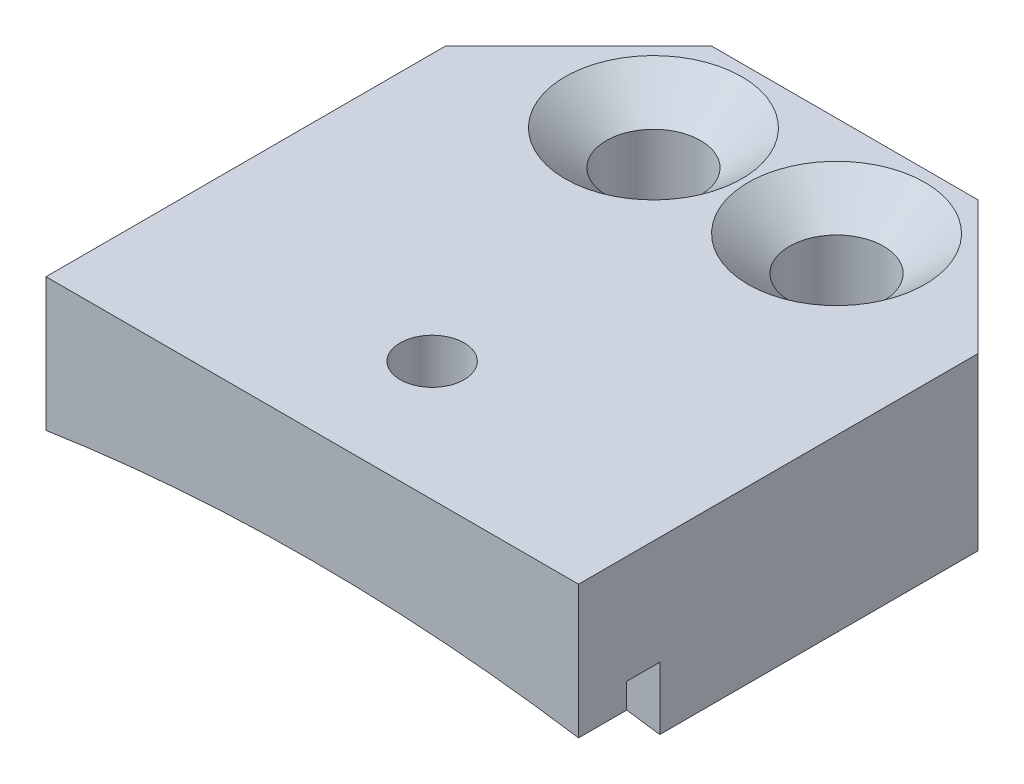
SolidWorks part; units mm, degrees
ref_plane "Front Plane" through (0, 0, 0) normal (0, 0, 1) x (1, 0, 0)
ref_plane "Top Plane" through (0, 0, 0) normal (0, 1, 0) x (1, 0, 0)
ref_plane "Right Plane" through (0, 0, 0) normal (1, 0, 0) x (0, 0, -1)
sketch "Sketch1" plane through (0, 0, 0) normal (0, 1, 0) x (1, 0, 0)
  line L0 (-28.5118, 6.4953) -> (-22.1618, 12.8453)
  line L1 (-22.1618, 12.8453) -> (-9.4618, 12.8453)
  line L2 (-28.5118, 6.4953) -> (-28.5118, -12.5547)
  line L3 (-28.5118, -12.5547) -> (-3.1118, -12.5547)
  line L4 (-3.1118, 6.4953) -> (-3.1118, -12.5547)
  line L5 (-9.4618, 12.8453) -> (-3.1118, 6.4953)
  line L6 (-15.8118, -12.5547) -> (-15.8118, 12.8453) construction
  line L8 (-3.1118, 6.4953) -> (-3.1118, 12.8453) construction
  line L9 (-3.1118, 12.8453) -> (-9.4618, 12.8453) construction
  dimension "D1" = 12.7
  dimension "D2" = 25.4
  dimension "D3" = 25.4
extrude "Boss-Extrude1" add sketch "Sketch1" along normal blind 6.35
sketch "Sketch2" plane through (0, 0, 12.5547) normal (0, 0, 1) x (1, 0, 0)
  circle A0 centre (-15.8118, -82.8523) radius 83.82
  dimension "D1" = 167.64
extrude "Cut-Extrude1" cut sketch "Sketch2" against normal through all both and the other way through all
sketch "Sketch5" plane through (0, 0, -12.8453) normal (0, 0, -1) x (-1, 0, 0)
  line L0 (3.1118, 6.35) -> (3.1118, 0) construction
  line L1 (3.1118, 6.35) -> (3.1118, 0)
  line L4 (28.5118, 6.35) -> (28.5118, 0) construction
  line L5 (28.5118, 6.35) -> (28.5118, 0)
  line L6 (28.5118, -1.7992) -> (28.5118, 0)
  line L7 (3.1118, -1.7992) -> (3.1118, 0)
  line L8 (3.1118, 6.35) -> (28.5118, 6.35)
  arc A0 (3.1118, -1.7992) -> (28.5118, -1.7992) centre (15.8118, -82.8523) cw
  arc A1 (28.5118, 0) -> (3.1118, 0) centre (15.8118, -82.8523) ccw construction
  arc A2 (28.5118, 0) -> (3.1118, 0) centre (15.8118, -82.8523) ccw construction
  dimension "D1" = 82.042
extrude "Boss-Extrude2" add sketch "Sketch5" against normal blind 22.225
chamfer "Chamfer1" distance 6.35 angle 45 2 edges at (-28.5118, 2.2754, -12.8453) (-3.1118, 2.2754, -12.8453)
hole_wizard "CSK for #8 Flat Head Machine Screw (100)1" positions "Sketch3" profile "Sketch4" countersink size "#8" standard "ANSI Inch" end condition through all
sketch "Sketch3" plane through (0, 6.35, 0) normal (0, 1, 0) x (1, 0, 0)
  line L0 (-15.8118, 12.8453) -> (-15.8118, 3.4006) construction
  line L1 (-9.4618, 12.8453) -> (-22.1618, 12.8453) construction
  point P0 (-20.1775, 8.0828)
  point P12 (-11.4462, 8.0828)
  dimension "D1" = 4.7625
  dimension "D2" = 4.3656
sketch "Sketch4" plane through (-20.1775, 6.35, -8.0828) normal (1, 0, 0) x (0, 0, 1)
  line L0 (0, 0) -> (0, 8.1492)
  line L1 (0, 8.1492) -> (2.2479, 8.1492)
  line L2 (2.2479, 8.1492) -> (2.2479, 1.6518)
  line L3 (2.2479, 1.6518) -> (4.2164, 0)
  line L5 (4.2164, 0) -> (0, 0)
  line L6 (-2.2479, 1.6518) -> (-4.2164, 0) construction
  line L11 (0, -6.35) -> (0, 107.95) construction
  dimension "Thru Hole Dia." = 4.4958
  dimension "Thru Hole Depth" = 8.1492
  dimension "Near C'Sink Dia." = 8.4328
  dimension "Near C'Sink Angle" = 100
sketch "Sketch6" plane through (0, 6.35, 0) normal (0, 1, 0) x (1, 0, 0)
  circle A0 centre (-15.8102, -6.8397) radius 1.524 construction
  circle A1 centre (-15.8102, -6.8397) radius 1.524
extrude "Cut-Extrude2" cut sketch "Sketch6" against normal through all
sketch "Sketch7" plane through (-3.1118, 0, 0) normal (1, 0, 0) x (0, 0, -1)
  line L0 (-12.5547, 6.35) -> (-12.5547, 0) construction
  line L1 (-8.6812, -1.7992) -> (-10.2687, -1.7992)
  line L2 (-8.6812, -1.7992) -> (-8.6812, 1.1906)
  line L3 (-8.6812, 1.1906) -> (-10.2687, 1.1906)
  line L4 (-10.2687, -1.7992) -> (-10.2687, 1.1906)
  line L5 (-9.3797, -1.7992) -> (6.4953, -1.7992) construction
  line L6 (-12.5547, 0) -> (-9.3797, 0) construction
  point P5 (0, 0)
  dimension "D1" = 1.5875
  dimension "D2" = 1.1906
  dimension "D3" = 2.286
extrude "Cut-Extrude3" cut sketch "Sketch7" against normal through all
